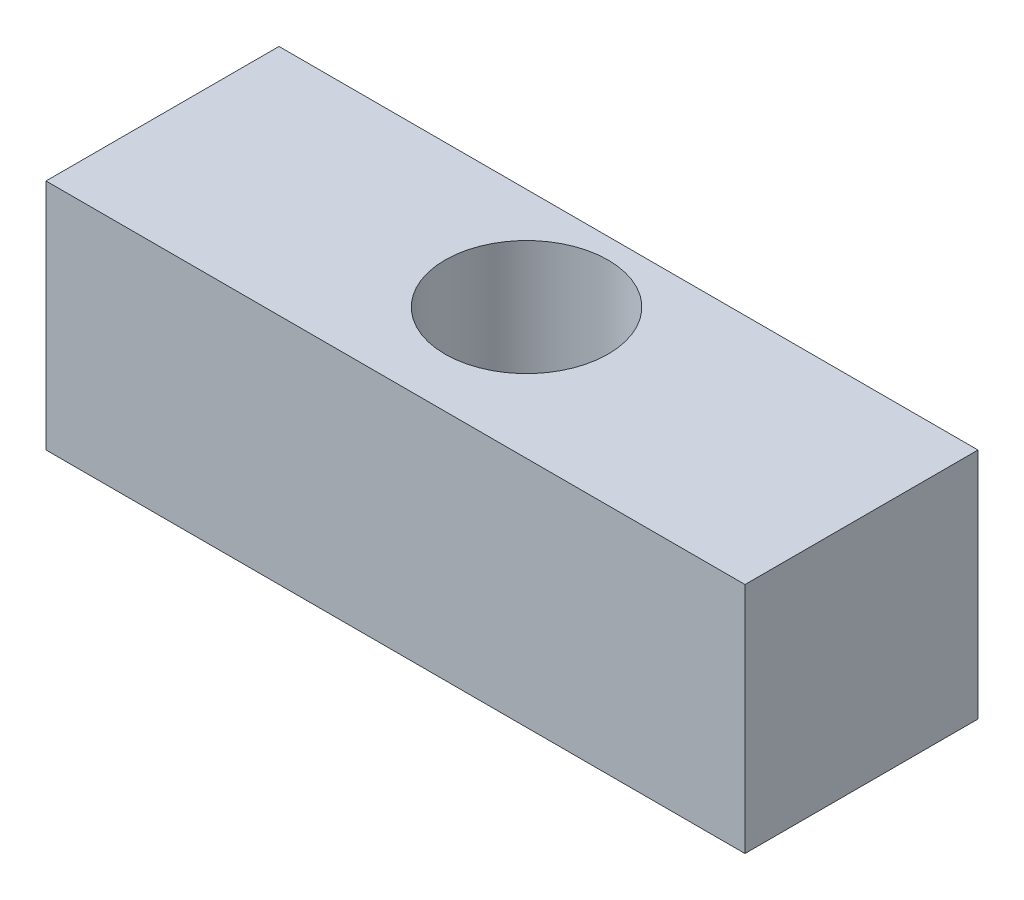
SolidWorks part; units mm, degrees
material "Polyethylene Cross-Linked"
ref_plane "Front Plane" through (0, 0, 0) normal (0, 0, 1) x (1, 0, 0)
ref_plane "Top Plane" through (0, 0, 0) normal (0, 1, 0) x (1, 0, 0)
ref_plane "Right Plane" through (0, 0, 0) normal (1, 0, 0) x (0, 0, -1)
sketch "Sketch1" plane through (0, 0, 0) normal (0, 1, 0) x (1, 0, 0)
  line L1 (0, 0) -> (38.1, 0)
  line L2 (0, 0) -> (0, 12.7)
  line L3 (0, 12.7) -> (38.1, 12.7)
  line L4 (38.1, 0) -> (38.1, 12.7)
  circle A0 centre (19.05, 7.1437) radius 4.445
extrude "Boss-Extrude1" add sketch "Sketch1" along normal blind 12.7
